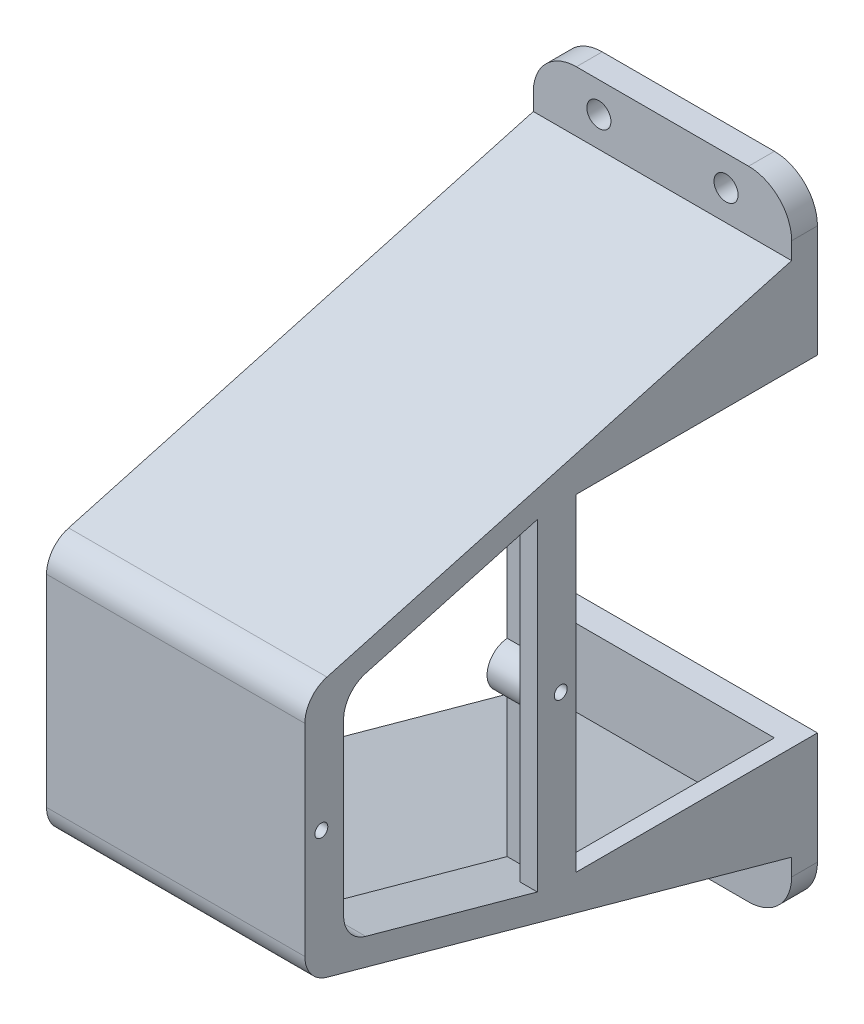
SolidWorks part; units mm, degrees
material "PET"
ref_plane "Plan de face" through (0, 0, 0) normal (0, 0, 1) x (1, 0, 0)
ref_plane "Plan de dessus" through (0, 0, 0) normal (0, 1, 0) x (1, 0, 0)
ref_plane "Plan de droite" through (0, 0, 0) normal (1, 0, 0) x (0, 0, -1)
sketch "Esquisse2" plane through (-46.7297, 0, -4) normal (1, 0, 0) x (0, 1, 0)
  line L0 (-49.8378, 4) -> (-40.5539, 4)
  line L1 (-40.5539, 4) -> (-32.8137, 32.0349)
  line L2 (-12.8378, 63.5349) -> (-12.8378, 59.0349) construction
  line L3 (-12.8378, 4) -> (-12.8378, 75.1995) construction
  line L4 (-32.8137, 32.0349) -> (7.138, 32.0349)
  line L5 (-42.8378, 7) -> (-27.2291, 63.5349)
  line L6 (-31.5713, 36.5349) -> (5.8956, 36.5349)
  line L7 (-12.8378, 32.0349) -> (-12.8378, 36.5349) construction
  line L8 (-42.8378, 4) -> (-51.8378, 4) construction
  line L9 (-49.8378, 7) -> (-42.8378, 7)
  line L10 (-23.8378, 29.0349) -> (-1.8378, 29.0349) construction
  line L11 (-49.8378, 4) -> (-49.8378, 7)
  line L12 (-25.8378, 4) -> (-42.8378, 4) construction
  line L13 (-27.2291, 63.5349) -> (1.5534, 63.5349)
  line L14 (-25.3593, 59.0349) -> (-0.3164, 59.0349)
  line L15 (-22.8378, 4) -> (-2.8378, 4) construction
  line L16 (-31.5713, 36.5349) -> (-25.3593, 59.0349)
  line L17 (24.1622, 7) -> (17.1622, 7)
  line L18 (24.1622, 4) -> (24.1622, 7)
  line L19 (24.1622, 4) -> (14.8782, 4)
  line L20 (14.8782, 4) -> (7.138, 32.0349)
  line L21 (17.1622, 7) -> (1.5534, 63.5349)
  line L22 (5.8956, 36.5349) -> (-0.3164, 59.0349)
  dimension "D5" = 3
  dimension "D6" = 59.5349
  dimension "D7" = 3
  dimension "D1" = 3
  dimension "D2" = 4.5
  dimension "D3" = 2
  dimension "D4" = 3
  dimension "D8" = 4.5
  dimension "D11" = 7
extrude "Boss.-Extru.1" add sketch "Esquisse2" against normal up to surface (30 mm away)
fillet "Congé5" radius 3.5 4 edges at (-61.7297, 1.5534, 59.5349) (-61.7297, -27.2291, 59.5349) (-61.7297, -25.3593, 55.0349) (-61.7297, -0.3164, 55.0349)
sketch "Esquisse3" plane through (0, 0, 3) normal (0, 0, 1) x (1, 0, 0)
  line L0 (-61.7297, 17.1622) -> (-61.7297, 24.1622) construction
  line L3 (-61.7297, 20.6622) -> (-76.7297, 20.6622) construction
  line L4 (-76.7297, 24.1622) -> (-76.7297, 17.1622) construction
  line L5 (-76.7297, -12.8378) -> (-46.7297, -12.8378) construction
  line L6 (-76.7297, -1.1112) -> (-76.7297, -24.5645) construction
  line L7 (-46.7297, -1.1112) -> (-46.7297, -24.5645) construction
  line L8 (-76.7297, 17.1622) -> (-46.7297, 17.1622) construction
  line L9 (-76.7297, 24.1622) -> (-46.7297, 24.1622) construction
  circle A0 centre (-69.2297, 20.6622) radius 1.5
  circle A1 centre (-54.2297, 20.6622) radius 1.5
  circle A2 centre (-54.2297, -46.3378) radius 1.5
  circle A3 centre (-69.2297, -46.3378) radius 1.5
  dimension "D1" = 3
extrude "Enlèv. mat.-Extru.1" cut sketch "Esquisse3" against normal through all
shell "Coque5" thickness 2 removed face at (-61.7297, -36.6838, 14.0175) removed face at (-61.7297, -12.8378, 28.0349) removed face at (-61.7297, 11.0081, 14.0175) removed face at (-61.7297, -12.8378, 32.5349) removed face at (-61.7297, -28.8199, 42.5006) removed face at (-61.7297, 3.1442, 42.5006) removed face at (-61.7297, -1.0775, 54.0352) removed face at (-61.7297, -12.8378, 55.0349) removed face at (-61.7297, -24.5981, 54.0352)
sketch "Esquisse6" plane through (-48.7297, 0, 0) normal (-1, 0, 0) x (0, 0, 1)
  line L0 (56.4341, -26.0104) -> (2, -41.0391) construction
  line L1 (2, 15.3634) -> (56.4341, 0.3347) construction
  line L2 (28.0349, -32.8137) -> (28.0349, 7.138) construction
  line L3 (32.5349, -31.5713) -> (32.5349, 5.8956) construction
  line L4 (32.5349, -32.6087) -> (28.0349, -33.8511)
  line L5 (28.0349, 8.1754) -> (32.5349, 6.933)
  line L6 (28.0349, -33.8511) -> (28.0349, 8.1754)
  line L7 (32.5349, -32.6087) -> (32.5349, 6.933)
extrude "Boss.-Extru.5" add sketch "Esquisse6" along normal blind 4
sketch "Esquisse7" plane through (-48.7297, 0, 0) normal (-1, 0, 0) x (0, 0, 1)
  line L0 (32.5349, 6.933) -> (32.5349, 5.8956)
  line L8 (56.4341, 0.3347) -> (32.5349, 6.933)
  line L9 (32.5349, 6.933) -> (32.5349, 5.8956)
  line L10 (32.5349, 5.8956) -> (52.4664, 0.3927)
  line L11 (55.0349, -2.981) -> (55.0349, -22.6946)
  line L12 (52.4664, -26.0684) -> (32.5349, -31.5713)
  line L13 (32.5349, -31.5713) -> (32.5349, -32.6087)
  line L14 (32.5349, -32.6087) -> (56.4341, -26.0104)
  line L15 (57.5349, -24.5645) -> (57.5349, -1.1112)
  line L16 (56.4341, 0.3347) -> (32.5349, 6.933)
  line L17 (32.5349, 6.933) -> (32.5349, 5.8956)
  line L18 (32.5349, 5.8956) -> (52.4664, 0.3927)
  line L19 (55.0349, -2.981) -> (55.0349, -22.6946)
  line L20 (52.4664, -26.0684) -> (32.5349, -31.5713)
  line L21 (32.5349, -31.5713) -> (32.5349, -32.6087)
  line L22 (32.5349, -32.6087) -> (56.4341, -26.0104)
  line L23 (57.5349, -24.5645) -> (57.5349, -1.1112)
  arc A4 (55.0349, -2.981) -> (52.4664, 0.3927) centre (51.5349, -2.981) ccw
  arc A5 (52.4664, -26.0684) -> (55.0349, -22.6946) centre (51.5349, -22.6946) ccw
  arc A6 (56.4341, -26.0104) -> (57.5349, -24.5645) centre (56.0349, -24.5645) ccw
  arc A7 (57.5349, -1.1112) -> (56.4341, 0.3347) centre (56.0349, -1.1112) ccw
  arc A8 (55.0349, -2.981) -> (52.4664, 0.3927) centre (51.5349, -2.981) ccw
  arc A9 (52.4664, -26.0684) -> (55.0349, -22.6946) centre (51.5349, -22.6946) ccw
  arc A10 (56.4341, -26.0104) -> (57.5349, -24.5645) centre (56.0349, -24.5645) ccw
  arc A11 (57.5349, -1.1112) -> (56.4341, 0.3347) centre (56.0349, -1.1112) ccw
  dimension "D1" = 0
extrude "Boss.-Extru.6" add sketch "Esquisse7" along normal blind 4 contours L23 A11 L16 L0 L18 A8 L19 A9 L20 L21 L22 A10 region at (-48.7297, 3.1829, 44.36)
sketch "Esquisse9" plane through (-74.7297, 0, 0) normal (1, 0, 0) x (0, 0, -1)
  line L8 (-2, 15.3634) -> (-56.4341, 0.3347)
  line L9 (-57.5349, -1.1112) -> (-57.5349, -24.5645)
  line L10 (-56.4341, -26.0104) -> (-2, -41.0391)
  line L11 (-2, -41.0391) -> (-2, -40.0017)
  line L12 (-2, -40.0017) -> (-28.0349, -32.8137)
  line L13 (-28.0349, -32.8137) -> (-28.0349, 7.138)
  line L14 (-28.0349, 7.138) -> (-2, 14.326)
  line L15 (-2, 14.326) -> (-2, 15.3634)
  line L16 (-2, 15.3634) -> (-56.4341, 0.3347)
  line L17 (-57.5349, -1.1112) -> (-57.5349, -24.5645)
  line L18 (-56.4341, -26.0104) -> (-2, -41.0391)
  line L19 (-2, -41.0391) -> (-2, -40.0017)
  line L20 (-2, -40.0017) -> (-28.0349, -32.8137)
  line L21 (-28.0349, -32.8137) -> (-28.0349, 7.138)
  line L22 (-28.0349, 7.138) -> (-2, 14.326)
  line L23 (-2, 14.326) -> (-2, 15.3634)
  arc A2 (-56.4341, 0.3347) -> (-57.5349, -1.1112) centre (-56.0349, -1.1112) ccw
  arc A3 (-57.5349, -24.5645) -> (-56.4341, -26.0104) centre (-56.0349, -24.5645) ccw
  arc A4 (-56.4341, 0.3347) -> (-57.5349, -1.1112) centre (-56.0349, -1.1112) ccw
  arc A5 (-57.5349, -24.5645) -> (-56.4341, -26.0104) centre (-56.0349, -24.5645) ccw
  dimension "D1" = 0
extrude "Enlèv. mat.-Extru.5" cut sketch "Esquisse9" against normal up to surface (2 mm away) up to face at (-76.7297, -12.8378, 21.5865)
sketch "Esquisse11" plane through (0, -49.8378, 0) normal (0, -1, 0) x (1, 0, 0)
  line L4 (-46.7297, 3) -> (-76.7297, 3)
  line L5 (-76.7297, 3) -> (-76.7297, 0)
  line L6 (-76.7297, 0) -> (-46.7297, 0)
  line L7 (-46.7297, 0) -> (-46.7297, 3)
  line L8 (-46.7297, 3) -> (-76.7297, 3)
  line L9 (-76.7297, 3) -> (-76.7297, 0)
  line L10 (-76.7297, 0) -> (-46.7297, 0)
  line L11 (-46.7297, 0) -> (-46.7297, 3)
  dimension "D1" = 0
extrude "Boss.-Extru.8" add sketch "Esquisse11" against normal blind 18
ref_plane "Symétrie" through (0, -12.8378, 0) normal (0, 1, 0) x (1, 0, 0)
sketch "Esquisse12" plane through (-46.7297, 0, 0) normal (1, 0, 0) x (0, 0, -1)
  line L0 (-28.0349, -31.8378) -> (-3, -31.8378)
  line L1 (-28.0349, 8.1754) -> (-28.0349, -33.8511) construction
rib "Nervure1" sketch "Esquisse12" sketch "Esquisse12" thickness 2 extrusion direction parallel to sketch draft on no parameters "D1"=2
mirror "Symétrie1" about plane through (0, -12.8378, 0) normal (0, 1, 0) of "Nervure1", "Boss.-Extru.8"
sketch "Esquisse13" plane through (-46.7297, 0, 0) normal (1, 0, 0) x (0, 0, -1)
  line L0 (16.5, -12.8378) -> (-16.5, -12.8378) construction
  circle A0 centre (-57.6188, -12.8378) radius 0.75
  circle A2 centre (-29.8188, -12.8378) radius 0.75
  dimension "D1" = 1.5
  dimension "D2" = 1.5
  dimension "D3" = 27.8
extrude "Enlèv. mat.-Extru.6" cut sketch "Esquisse13" against normal blind 8
sketch "Esquisse15" plane through (-52.7297, 0, 0) normal (-1, 0, 0) x (0, 0, 1)
  line L0 (57.5349, -24.5645) -> (57.5349, -13.5831) construction
  line L1 (57.5349, -15.3865) -> (57.5349, -13.5831)
  line L2 (57.5349, -12.0925) -> (57.5349, -1.1112) construction
  line L3 (57.5349, -12.0925) -> (57.5349, -10.2892)
  arc A1 (57.5349, -12.0925) -> (57.5349, -13.5831) centre (57.6188, -12.8378) ccw construction
  arc A2 (57.3335, -10.3038) -> (57.3335, -15.3718) centre (57.6188, -12.8378) ccw
  arc A3 (57.5349, -10.2892) -> (57.5349, -15.3865) centre (57.6188, -12.8378) ccw
  arc A4 (57.5349, -12.0925) -> (57.5349, -13.5831) centre (57.6188, -12.8378) ccw
  dimension "D1" = 1.8
extrude "Boss.-Extru.9" add sketch "Esquisse15" along normal blind 6
sketch "Esquisse16" plane through (-58.7297, 0, 0) normal (-1, 0, 0) x (0, 0, 1)
  line L0 (57.5349, -12.0925) -> (57.5349, -10.2892) construction
  line L1 (57.5349, -15.3865) -> (57.5349, -10.2892)
  arc A0 (57.5349, -10.2892) -> (57.5349, -15.3865) centre (57.6188, -12.8378) ccw construction
  arc A1 (57.5349, -10.2892) -> (57.5349, -15.3865) centre (57.6188, -12.8378) ccw
extrude "Boss.-Extru.10" add sketch "Esquisse16" along normal blind 2.5
fillet "Congé7" radius 2 1 edges at (-61.2297, -12.8378, 55.0688)
sketch "Esquisse17" plane through (-52.7297, 0, 0) normal (-1, 0, 0) x (0, 0, 1)
  line L0 (28.0349, 8.1754) -> (28.0349, -33.8511) construction
  line L1 (28.0349, -11.0157) -> (28.0349, -14.2723) construction
  line L2 (32.5349, 5.8956) -> (52.4664, 0.3927) construction
  line L3 (30.0349, 6.5859) -> (32.5349, 5.8956)
  line L4 (52.4664, -26.0684) -> (32.5349, -31.5713) construction
  line L5 (32.5349, -31.5713) -> (30.0349, -32.2615)
  line L6 (30.0349, 6.5859) -> (30.0349, -10.297)
  line L7 (32.5349, -31.5713) -> (32.5349, 5.8956) construction
  line L8 (30.0349, -15.3787) -> (30.0349, -32.2615)
  line L9 (32.5349, -31.5713) -> (32.5349, 5.8956)
  circle A3 centre (29.8188, -12.8378) radius 2.55
  arc A4 (30.0349, -15.3787) -> (30.0349, -10.297) centre (29.8188, -12.8378) ccw
  dimension "D1" = 2
  dimension "D2" = 1.8
extrude "Enlèv. mat.-Extru.7" cut sketch "Esquisse17" against normal offset from surface (4 mm away) 2 up to face at (-46.7297, -12.8378, 29.0688)
fillet "Congé9" radius 5 4 edges at (-76.7297, 24.1622, 1.5) (-76.7297, -49.8378, 1.5) (-46.7297, -49.8378, 1.5) (-46.7297, 24.1622, 1.5)
sketch "Esquisse22" plane through (0, 0, 3) normal (0, 0, 1) x (1, 0, 0)
  line L0 (-61.7297, 17.1622) -> (-61.7297, 24.1622) construction
  line L1 (-76.7297, 17.1622) -> (-46.7297, 17.1622) construction
  line L2 (-71.7297, 24.1622) -> (-51.7297, 24.1622) construction
  line L3 (-61.7297, 20.6622) -> (-76.4994, 20.6622) construction
  line L4 (-76.7297, -12.8378) -> (-46.7297, -12.8378) construction
  line L5 (-76.7297, -1.1112) -> (-76.7297, -24.5645) construction
  line L6 (-46.7297, -1.1112) -> (-46.7297, -24.5645) construction
  circle A0 centre (-69.1146, 20.6622) radius 1.4
  arc A1 (-71.7297, 24.1622) -> (-76.7297, 19.1622) centre (-71.7297, 19.1622) ccw construction
  circle A2 centre (-54.3449, 20.6622) radius 1.4
  circle A3 centre (-54.3449, -46.3378) radius 1.4
  circle A4 centre (-69.1146, -46.3378) radius 1.4
  dimension "D1" = 2.8
extrude "Enlèv. mat.-Extru.8" cut sketch "Esquisse22" against normal through all
